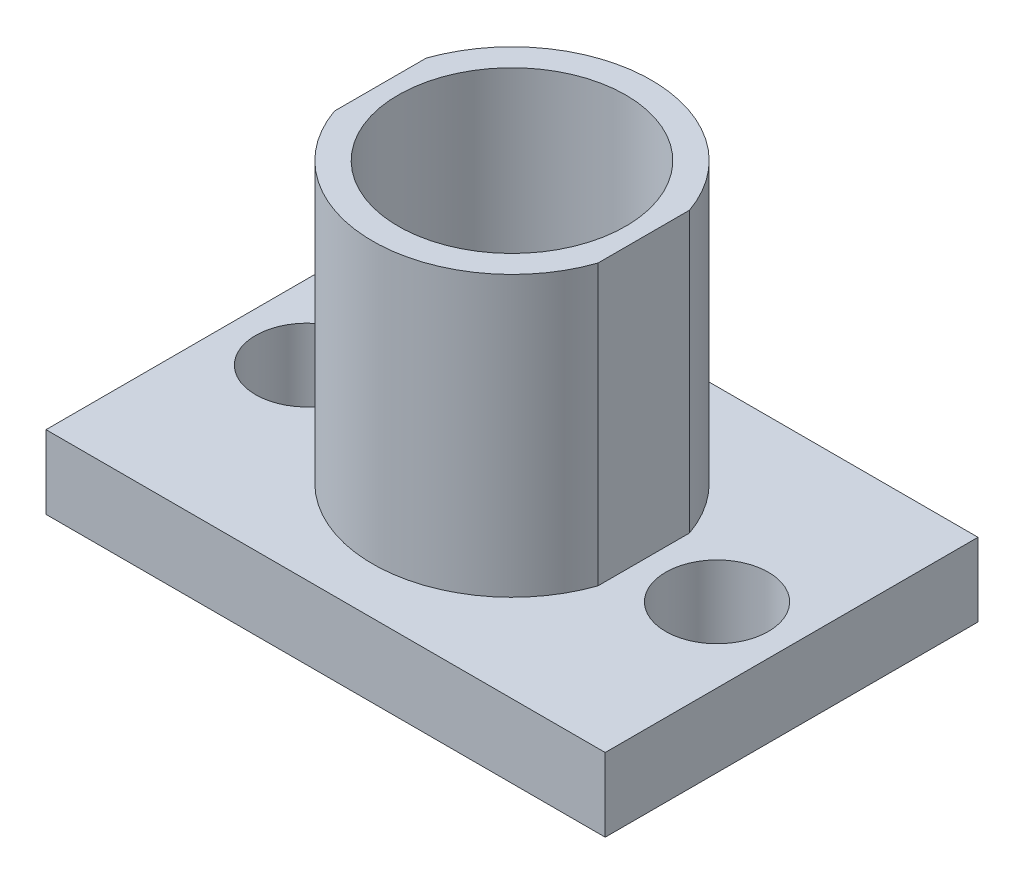
SolidWorks part; units mm, degrees
ref_plane "前视" through (0, 0, 0) normal (0, 0, 1) x (1, 0, 0)
ref_plane "上视" through (0, 0, 0) normal (0, 1, 0) x (1, 0, 0)
ref_plane "右视" through (0, 0, 0) normal (1, 0, 0) x (0, 0, -1)
sketch "Sketch1" plane through (0, 0, 0) normal (0, 1, 0) x (1, 0, 0)
  line L1 (-25.8417, 12.7) -> (12.2583, 12.7)
  line L2 (-25.8417, 12.7) -> (-25.8417, -12.7)
  line L3 (-25.8417, -12.7) -> (12.2583, -12.7)
  line L4 (12.2583, 12.7) -> (12.2583, -12.7)
  dimension "D1" = 25.4
  dimension "D2" = 38.1
extrude "Boss-Extrude1" add sketch "Sketch1" along normal blind 5
ref_point "Point1"
sketch "Sketch3" plane through (0, 5, 0) normal (0, 1, 0) x (1, 0, 0)
  circle A0 centre (-6.7917, 0) radius 9.5
  circle A1 centre (-6.7917, 0) radius 7.75
  dimension "D1" = 19
  dimension "D2" = 15.5
extrude "Boss-Extrude2" add sketch "Sketch3" along normal blind 19.05
ref_axis "Axis1" through (12.2583, 5, 0) along (-1, 0, 0)
sketch "Sketch4" plane through (0, 5, 0) normal (0, 1, 0) x (1, 0, 0)
  line L0 (12.2583, -12.7) -> (12.2583, 12.7) construction
  line L1 (-25.8417, 12.7) -> (-25.8417, -12.7) construction
  circle A0 centre (7.1783, 0) radius 3.5
  circle A1 centre (-20.7617, 0) radius 3.5
  point P0 (7.1783, 0)
  point P1 (12.2583, 0)
  point P4 (-20.7617, 0)
  dimension "D3" = 7
  dimension "D4" = 7
  dimension "D1" = 5.08
  dimension "D2" = 5.08
extrude "Cut-Extrude1" cut sketch "Sketch4" against normal through all
sketch "Sketch5" plane through (0, 5, 0) normal (0, 1, 0) x (1, 0, 0)
  line L0 (-6.7917, 0) -> (-6.7917, -6.4335) construction
  line L1 (-17.3636, 4.5849) -> (-15.7636, 4.5849)
  line L2 (-17.3636, 4.5849) -> (-17.3636, -5.4151)
  line L3 (-17.3636, -5.4151) -> (-15.7636, -5.4151)
  line L4 (-15.7636, 4.5849) -> (-15.7636, -5.4151)
  line L5 (3.7802, -5.4151) -> (2.1802, -5.4151)
  line L6 (2.1802, 4.5849) -> (2.1802, -5.4151)
  line L7 (3.7802, 4.5849) -> (3.7802, -5.4151)
  line L8 (3.7802, 4.5849) -> (2.1802, 4.5849)
  dimension "D1" = 1.6
  dimension "D2" = 10
extrude "Cut-Extrude2" cut sketch "Sketch5" along normal through all
